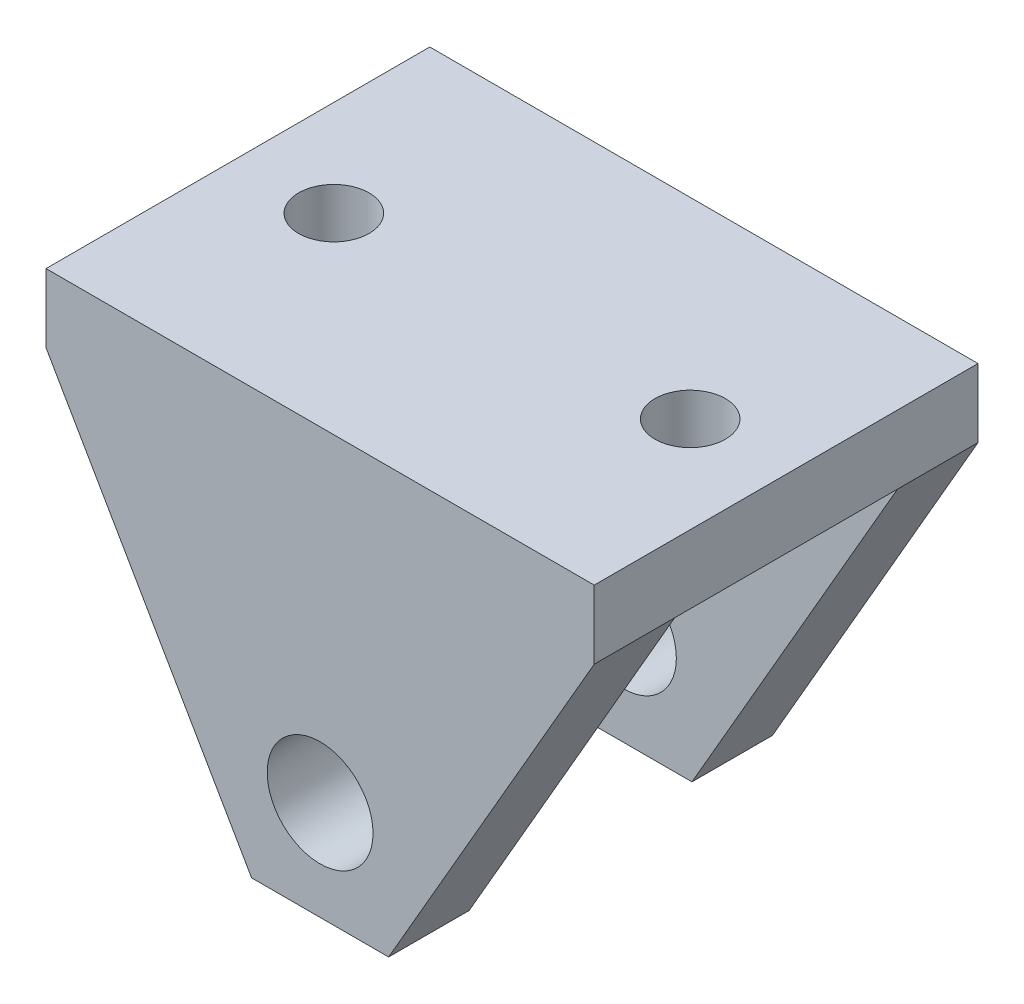
SolidWorks part; units mm, degrees
material "6061-T6 (SS)"
ref_plane "Front Plane" through (0, 0, 0) normal (0, 0, 1) x (1, 0, 0)
ref_plane "Top Plane" through (0, 0, 0) normal (0, 1, 0) x (1, 0, 0)
ref_plane "Right Plane" through (0, 0, 0) normal (1, 0, 0) x (0, 0, -1)
sketch "Sketch2" plane through (0, 0, 0) normal (0, 1, 0) x (1, 0, 0)
  line L0 (0, 0) -> (0, 13.439) construction
  line L1 (0, 0) -> (15.2263, 0) construction
  line L3 (-25.4, 17.78) -> (25.4, 17.78)
  line L4 (-25.4, 17.78) -> (-25.4, -17.78)
  line L5 (-25.4, -17.78) -> (25.4, -17.78)
  line L6 (25.4, 17.78) -> (25.4, -17.78)
  circle A0 centre (-16.51, 0) radius 3.2639
  circle A2 centre (16.51, 0) radius 3.2639
  dimension "D5" = 6.5278
  dimension "D6" = 16.51
  dimension "D1" = 50.8
  dimension "D2" = 25.4
  dimension "D3" = 35.56
  dimension "D4" = 17.78
extrude "Boss-Extrude1" add sketch "Sketch2" against normal blind 39.37
sketch "Sketch4" plane through (0, 0, 17.78) normal (0, 0, 1) x (1, 0, 0)
  line L0 (-25.4, -6.35) -> (-6.35, -39.37)
  line L1 (-25.4, -39.37) -> (-25.4, 0) construction
  line L2 (-25.4, -39.37) -> (25.4, -39.37) construction
  line L3 (-6.35, -39.37) -> (-25.4, -39.37)
  line L4 (-25.4, -39.37) -> (-25.4, -6.35)
  line L5 (0, 0) -> (0, 16.2985) construction
  line L6 (-25.4, 0) -> (25.4, 0) construction
  line L7 (6.35, -39.37) -> (25.4, -39.37)
  line L8 (25.4, -6.35) -> (6.35, -39.37)
  line L9 (25.4, -39.37) -> (25.4, -6.35)
  circle A0 centre (0, -30.1714) radius 4.9022
  dimension "D3" = 9.8044
  dimension "D4" = 9.1986
  dimension "D1" = 6.35
  dimension "D2" = 6.35
extrude "Cut-Extrude1" cut sketch "Sketch4" against normal through all
sketch "Sketch5" plane through (0, -39.37, 0) normal (0, -1, 0) x (1, 0, 0)
  line L0 (-25.4, -17.78) -> (-25.4, 17.78) construction
  line L1 (-25.4, 10.3251) -> (25.4, 10.3251)
  line L2 (-25.4, 10.3251) -> (-25.4, -10.3251)
  line L3 (-25.4, -10.3251) -> (25.4, -10.3251)
  line L4 (25.4, 10.3251) -> (25.4, -10.3251)
  line L5 (25.4, -17.78) -> (25.4, 17.78) construction
  line L6 (0, 0) -> (0, 50000) construction
  line L7 (0, 0) -> (50000, 0) construction
  point P13 (25000, 0)
  dimension "D1" = 20.6502
  dimension "D2" = 10.3251
  dimension "D3" = 10.3251
extrude "Cut-Extrude2" cut sketch "Sketch5" against normal blind 33.02
